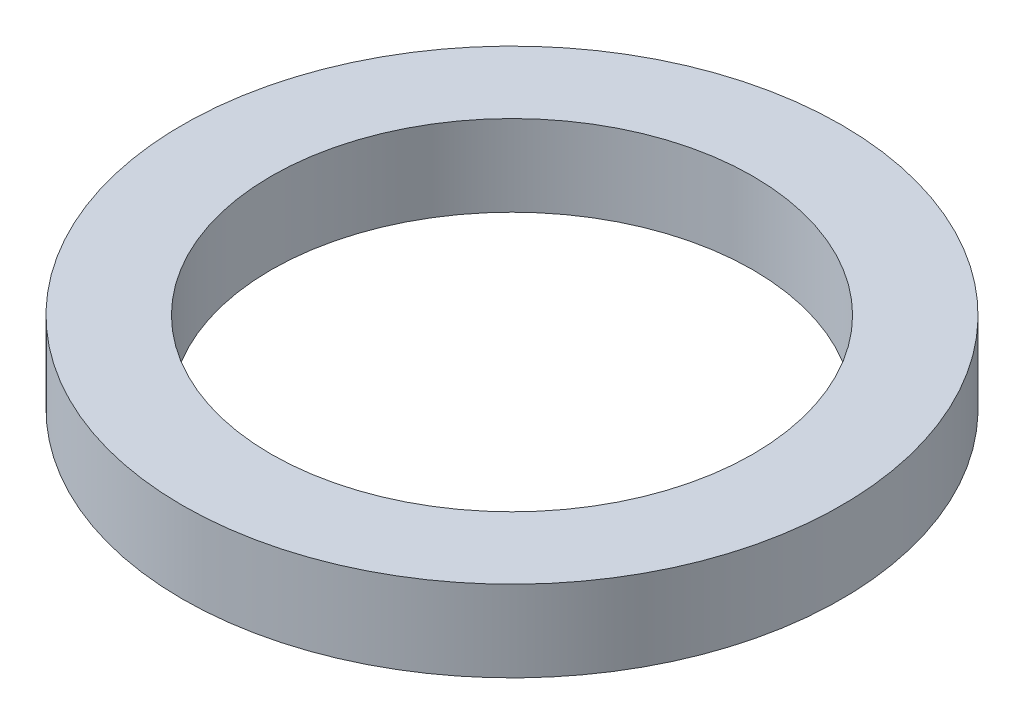
SolidWorks part; units mm, degrees
ref_plane "Front Plane" through (0, 0, 0) normal (0, 0, 1) x (1, 0, 0)
ref_plane "Top Plane" through (0, 0, 0) normal (0, 1, 0) x (1, 0, 0)
ref_plane "Right Plane" through (0, 0, 0) normal (1, 0, 0) x (0, 0, -1)
sketch "Sketch1" plane through (0, 0, 0) normal (0, 1, 0) x (1, 0, 0)
  circle A0 centre (0, 0) radius 65
  dimension "FLANGE_OD" = 130
extrude "Boss-Extrude1" add sketch "Sketch1" along normal blind 16
sketch "Sketch2" plane through (0, 0, 0) normal (0, 1, 0) x (1, 0, 0)
  circle A0 centre (0, 0) radius 47.5
  dimension "BORE_D" = 95
extrude "Cut-Extrude1" cut sketch "Sketch2" along normal through all
sketch "Sketch3" plane through (0, 16, 0) normal (0, 1, 0) x (1, 0, 0)
  circle A0 centre (0, 0) radius 26.6551 construction
  circle A1 centre (-26.6551, 0) radius 2.501
  dimension "BOLT_D" = 5.0021
  dimension "BOLT_PCD" = 53.3102
extrude "Cut-Extrude2" cut sketch "Sketch3" against normal blind 11.3594 rebuild error yes
pattern_circular "CirPattern1" count 8 over 360 rebuild error yes
